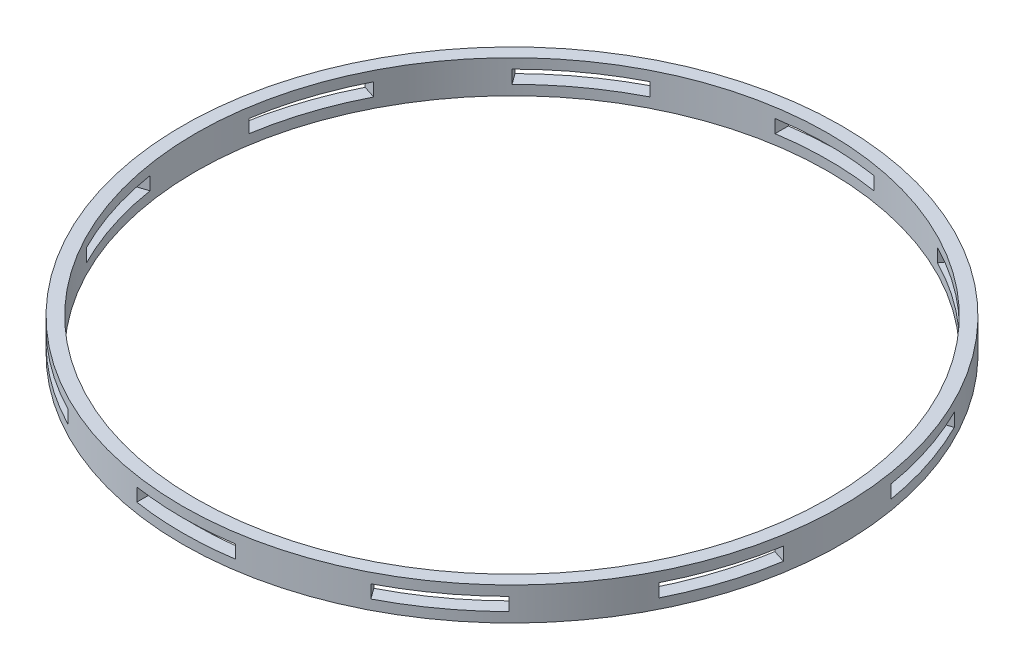
SolidWorks part; units mm, degrees
ref_plane "Front Plane" through (0, 0, 0) normal (0, 0, 1) x (1, 0, 0)
ref_plane "Top Plane" through (0, 0, 0) normal (0, 1, 0) x (1, 0, 0)
ref_plane "Right Plane" through (0, 0, 0) normal (1, 0, 0) x (0, 0, -1)
sketch "Sketch1" plane through (0, 0, 0) normal (0, 1, 0) x (1, 0, 0)
  line L0 (40.8443, 86.8778) -> (42.5461, 90.4977) construction
  circle A0 centre (0, 0) radius 96
  circle A1 centre (0, 0) radius 100
  dimension "D2" = 192
  dimension "D1" = 4
extrude "Boss-Extrude1" add sketch "Sketch1" along normal blind 10
sketch "Sketch2" plane through (0, 0, 0) normal (0, 0, 1) x (1, 0, 0)
  line L0 (-100, 0) -> (100, 0) construction
  line L1 (-15, 7) -> (15, 7)
  line L2 (-15, 7) -> (-15, 3)
  line L3 (-15, 3) -> (15, 3)
  line L4 (15, 7) -> (15, 3)
  line L5 (96, 10) -> (-96, 10) construction
  point P11 (0, 3)
  dimension "D1" = 3
  dimension "D2" = 3
  dimension "D3" = 30
extrude "Cut-Extrude1" cut sketch "Sketch2" against normal through all
ref_axis "Axis1" through (0, 10, 0) along (0, -1, 0)
pattern_circular "CirPattern1" count 10 over 360 about axis through (0, 10, 0) along (0, -1, 0) of "Cut-Extrude1"
